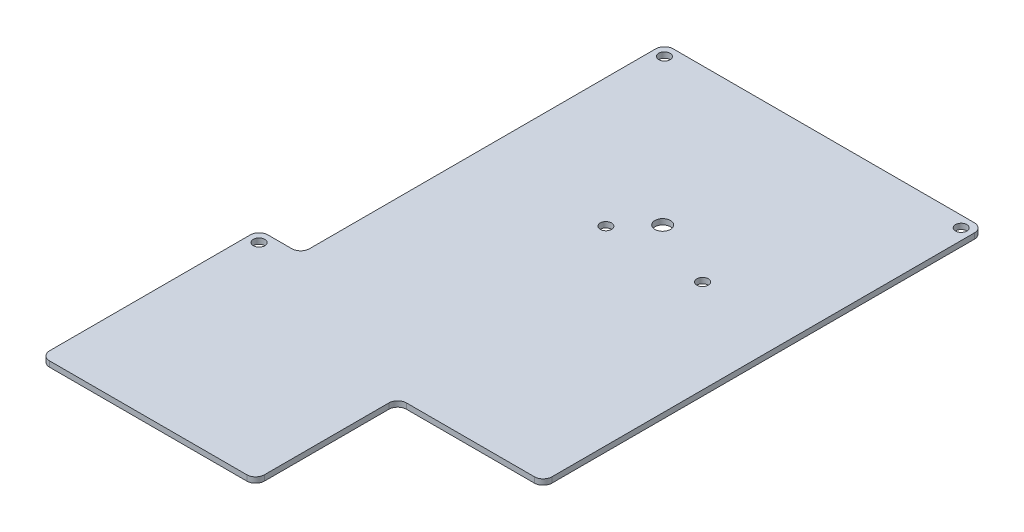
SolidWorks part; units mm, degrees
ref_plane "Front" through (0, 0, 0) normal (0, 0, 1) x (1, 0, 0)
ref_plane "Top" through (0, 0, 0) normal (0, 1, 0) x (1, 0, 0)
ref_plane "Right" through (0, 0, 0) normal (1, 0, 0) x (0, 0, -1)
sketch "Sketch1" plane through (0, 0, 0) normal (0, 1, 0) x (1, 0, 0)
  line L1 (-46, -63.5) -> (46, -63.5)
  line L2 (-46, -63.5) -> (-46, 63.5)
  line L3 (-46, 63.5) -> (46, 63.5)
  line L4 (46, -63.5) -> (46, 63.5)
  line L5 (-46, -63.5) -> (46, 63.5) construction
  line L6 (-46, 63.5) -> (46, -63.5) construction
  point P0 (0, 0)
  dimension "D1" = 127
  dimension "D2" = 92
extrude "Boss-Extrude1" add sketch "Sketch1" along normal blind 1.6
hole_wizard "#4 Clearance Hole1" positions "Sketch4" profile "Sketch5" hole size "#4" standard "ANSI Inch"
sketch "Sketch4" plane through (0, 1.6, 0) normal (0, 1, 0) x (1, 0, 0)
  line L2 (46, 63.5) -> (-46, 63.5) construction
  line L3 (-46, 63.5) -> (-46, -63.5) construction
  line L4 (-8.85, 9.46) -> (19.05, 9.46)
  point P22 (19.05, 9.46)
  point P24 (-8.85, 9.46)
  dimension "D1" = 27.9
  dimension "D3" = 54.04
  dimension "D4" = 37.15
sketch "Sketch5" plane through (19.05, 1.6, -9.46) normal (1, 0, 0) x (0, 0, 1)
  line L0 (0, 0) -> (0, 19.7306)
  line L1 (0, 19.7306) -> (1.6319, 18.75)
  line L2 (1.6319, 18.75) -> (1.6319, 0)
  line L5 (1.6319, 0) -> (0, 0)
  line L10 (0, 19.7306) -> (-1.632, 18.75) construction
  line L11 (0, -6.35) -> (0, 107.95) construction
  dimension "Hole Dia." = 3.2639
  dimension "Hole Depth" = 18.75
  dimension "Drill Angle" = 118
hole_wizard "#8 Clearance Hole1" positions "Sketch6" profile "Sketch7" hole size "#8" standard "ANSI Inch"
sketch "Sketch6" plane through (0, 0, 0) normal (0, -1, 0) x (-1, 0, 0)
  circle A1 centre (0.9676, 17.9647) radius 1.524 construction
  point P0 (0.9676, 17.9647)
sketch "Sketch7" plane through (-0.9676, 0, -17.9647) normal (1, 0, 0) x (0, 0, -1)
  line L0 (0, 0) -> (0, 20.1007)
  line L1 (0, 20.1007) -> (2.2479, 18.75)
  line L2 (2.2479, 18.75) -> (2.2479, 0)
  line L5 (2.2479, 0) -> (0, 0)
  line L10 (0, 20.1007) -> (-2.2479, 18.75) construction
  line L11 (0, -6.35) -> (0, 107.95) construction
  dimension "Hole Dia." = 4.4958
  dimension "Hole Depth" = 18.75
  dimension "Drill Angle" = 118
sketch "Sketch8" plane through (0, 0, 0) normal (0, 1, 0) x (1, 0, 0)
  line L0 (-46, -63.5) -> (46, -63.5) construction
  line L1 (4, -41.5) -> (-58, -41.5)
  line L2 (4, -41.5) -> (4, -104.5)
  line L3 (4, -104.5) -> (-58, -104.5)
  line L4 (-58, -41.5) -> (-58, -104.5)
  line L5 (4, -41.5) -> (-58, -104.5) construction
  line L6 (4, -104.5) -> (-58, -41.5) construction
  line L7 (-46, 63.5) -> (-46, -63.5) construction
  point P0 (-27, -73)
  dimension "D1" = 22
  dimension "D2" = 50
  dimension "D3" = 62
  dimension "D4" = 63
extrude "Boss-Extrude2" add sketch "Sketch8" along normal blind 1.6
hole_wizard "#4 Clearance Hole2" positions "Sketch2" profile "Sketch3" hole size "#4" standard "ANSI Inch"
sketch "Sketch2" plane through (0, 1.6, 0) normal (0, 1, 0) x (1, 0, 0)
  line L1 (-42.825, 60.325) -> (42.825, 60.325)
  line L2 (-42.825, 60.325) -> (-42.825, -60.325)
  line L3 (-42.825, -60.325) -> (42.825, -60.325)
  line L4 (42.825, 60.325) -> (42.825, -60.325)
  line L5 (-42.825, 60.325) -> (42.825, -60.325) construction
  line L6 (-42.825, -60.325) -> (42.825, 60.325) construction
  line L9 (46, -63.5) -> (46, 63.5) construction
  line L10 (4, -63.5) -> (46, -63.5) construction
  line L11 (-46, -41.5) -> (-58, -41.5) construction
  line L12 (-58, -41.5) -> (-58, -104.5) construction
  point P0 (-42.825, 60.325)
  point P2 (42.825, 60.325)
  point P118 (-54.82, -44.68)
  dimension "D1" = 3.175
  dimension "D2" = 3.175
  dimension "D3" = 3.18
  dimension "D4" = 3.18
sketch "Sketch3" plane through (-42.825, 1.6, -60.325) normal (1, 0, 0) x (0, 0, 1)
  line L0 (0, 0) -> (0, 50.9806)
  line L1 (0, 50.9806) -> (1.6319, 50)
  line L2 (1.6319, 50) -> (1.6319, 0)
  line L5 (1.6319, 0) -> (0, 0)
  line L10 (0, 50.9806) -> (-1.632, 50) construction
  line L11 (0, -6.35) -> (0, 107.95) construction
  dimension "Hole Dia." = 3.2639
  dimension "Hole Depth" = 50
  dimension "Drill Angle" = 118
fillet "Fillet1" radius 2.54 8 edges at (46, 0.8, 63.5) (46, 0.8, -63.5) (-46, 0.8, -63.5) (4, 0.8, 63.5) (4, 0.8, 104.5) (-58, 0.8, 104.5) (-58, 0.8, 41.5) (-46, 0.8, 41.5)
ref_point "PCB_ORIGIN"
sketch "TOP_KEEPOUT" plane through (0, 1.6, 0) normal (0, 1, 0) x (1, 0, 0)
  circle A0 centre (-8.85, 9.46) radius 3.429
  circle A1 centre (19.05, 9.46) radius 3.429
  circle A2 centre (42.825, 60.325) radius 3.429
  circle A3 centre (-42.825, 60.325) radius 3.429
  circle A6 centre (-54.82, -44.68) radius 3.429
  dimension "D1" = 6.858
sketch "BOTTOM_KEEPOUT" plane through (0, 0, 0) normal (0, -1, 0) x (1, 0, 0)
  line L1 (26.67, -45.02) -> (-26.7462, -45.02)
  line L2 (26.67, -45.02) -> (26.67, 56.58)
  line L3 (26.67, 56.58) -> (-26.7462, 56.58)
  line L4 (-26.7462, -45.02) -> (-26.7462, 56.58)
  line L5 (26.67, -41.464) -> (26.67, 55.056) construction
  line L6 (25.146, 56.58) -> (-25.2222, 56.58) construction
  line L8 (-26.7462, 55.056) -> (-26.7462, -40.7166) construction
  line L13 (-11.5062, -45.02) -> (23.114, -45.02) construction
  circle A2 centre (42.825, -60.325) radius 3.937
  circle A3 centre (-42.825, -60.325) radius 3.937
  circle A4 centre (-54.82, 44.68) radius 3.937
  dimension "D1" = 7.874
sketch "TOP_CONN_POS" plane through (0, 1.6, 0) normal (0, 1, 0) x (1, 0, 0)
  line L0 (6.35, -35.308) -> (6.35, -45.308)
  line L1 (-37.936, 28.7076) -> (-37.936, 18.7076)
  line L2 (1.35, -40.308) -> (11.35, -40.308)
  line L3 (-42.936, 23.7076) -> (-32.936, 23.7076)
  line L4 (0, 60.436) -> (0, 50.436)
  line L5 (-5, 55.436) -> (5, 55.436)
  line L6 (-37.936, -5.35) -> (-37.936, 52.7652) construction
  line L7 (-43.524, 23.7076) -> (-32.348, 23.7076) construction
  line L8 (0, 61.024) -> (0, 49.848) construction
  line L9 (-29.0576, 55.436) -> (29.0576, 55.436) construction
  line L10 (37.936, 28.7076) -> (37.936, 18.7076)
  line L11 (32.936, 23.7076) -> (42.936, 23.7076)
  line L12 (43.524, 23.7076) -> (32.348, 23.7076) construction
  line L13 (37.936, 52.7652) -> (37.936, -5.35) construction
  line L14 (37.936, -25.0576) -> (37.936, -35.0576)
  line L15 (32.936, -30.0576) -> (42.936, -30.0576)
  line L16 (37.936, -52.7652) -> (37.936, -7.35) construction
  line L17 (43.524, -30.0576) -> (32.348, -30.0576) construction
  line L18 (0, -50.436) -> (0, -60.436)
  line L19 (-5, -55.436) -> (5, -55.436)
  line L20 (29.0576, -55.436) -> (-29.0576, -55.436) construction
  line L21 (0, -61.024) -> (0, -49.848) construction
  line L22 (6.35, -45.896) -> (6.35, -34.72) construction
  line L23 (-16.3576, -40.308) -> (29.0576, -40.308) construction
  line L24 (-41.4, -141.4918) -> (-41.4, -151.4918)
  line L25 (-46.4, -146.4918) -> (-36.4, -146.4918)
  line L26 (-41.4, -167.6418) -> (-41.4, -157.6418)
  line L27 (-46.4, -162.6418) -> (-36.4, -162.6418)
  line L28 (-0.6, -67.345) -> (-0.6, -77.345)
  line L29 (-5.6, -72.345) -> (4.4, -72.345)
  line L30 (4, -72.345) -> (-11.4, -72.345) construction
  line L31 (-0.6, -77.67) -> (-0.6, -67.02) construction
  line L32 (-41.4, -155.8168) -> (-41.4, -169.4668) construction
  line L33 (-46, -162.6418) -> (-30.92, -162.6418) construction
  line L34 (-46, -146.4918) -> (-30.92, -146.4918) construction
  line L35 (-41.4, -139.6668) -> (-41.4, -153.3168) construction
  point P2 (6.35, -40.308)
  point P9 (-37.936, 23.7076)
  point P14 (0, 55.436)
  point P17 (-41.4, -146.4918)
  point P29 (37.936, 23.7076)
  point P40 (37.936, -30.0576)
  point P50 (0, -55.436)
  point P53 (-41.4, -162.6418)
  point P66 (-0.6, -72.345)
  dimension "D1" = 10
  dimension "D2" = 0
  dimension "D3" = 0
  dimension "D4" = 0
  dimension "D5" = 0
  dimension "D6" = 0
  dimension "D7" = 0
  dimension "D8" = 0
  dimension "D9" = 0
  dimension "D10" = 0
  dimension "D11" = 0
  dimension "D12" = 0
  dimension "D13" = 0
  dimension "D14" = 0
  dimension "D15" = 0
  dimension "D16" = 0
  dimension "D17" = 0
  dimension "D18" = 0
  dimension "D19" = 0
sketch "BOTTOM_CONN_POS" plane through (0, 1.6, 0) normal (0, 1, 0) x (1, 0, 0)
  line L2 (-41.7687, 26.7669) -> (-41.7687, 16.7669)
  line L3 (-46.7687, 21.7669) -> (-36.7687, 21.7669)
  line L4 (-17.2529, 63.5) -> (-17.2529, 48.1) construction
  line L5 (-25.5779, 58.9) -> (-8.9279, 58.9) construction
  line L6 (-41.7687, 45.4169) -> (-41.7687, 35.4169)
  line L7 (-46.7687, 40.4169) -> (-36.7687, 40.4169)
  line L8 (-41.7687, -41.17) -> (-41.7687, -51.17)
  line L9 (-46.7687, -46.17) -> (-36.7687, -46.17)
  line L10 (-41.7687, -53.82) -> (-41.7687, -63.82)
  line L11 (-46.7687, -58.82) -> (-36.7687, -58.82)
  line L12 (-41.7687, -66.47) -> (-41.7687, -76.47)
  line L13 (-46.7687, -71.47) -> (-36.7687, -71.47)
  line L14 (0.6971, 63.5) -> (0.6971, 48.1) construction
  line L15 (-46, -131.2896) -> (-30.6, -131.2896) construction
  line L16 (-46, -135.3418) -> (-30.6, -135.3418) construction
  line L17 (-46, -35.1047) -> (-30.6, -35.1047) construction
  line L18 (-39, -24.955) -> (-39, -34.955)
  line L19 (-44, -29.955) -> (-34, -29.955)
  line L32 (-39, -34.655) -> (-39, -25.255) construction
  line L33 (-42.65, -29.955) -> (-35.5, -29.955) construction
  line L40 (39.35, -41.555) -> (39.35, -51.555)
  line L41 (34.35, -46.555) -> (44.35, -46.555)
  line L42 (-41.4, 20.4523) -> (-41.4, 10.4523)
  line L43 (-46.4, 15.4523) -> (-36.4, 15.4523)
  line L44 (39.35, -24.455) -> (39.35, -34.455)
  line L45 (34.35, -29.455) -> (44.35, -29.455)
  line L46 (39.35, -39.355) -> (39.35, -53.755) construction
  line L47 (35.85, -46.555) -> (43, -46.555) construction
  line L48 (35.85, -29.455) -> (43, -29.455) construction
  line L49 (-41.4, 20.7773) -> (-41.4, 10.1273) construction
  line L50 (-46, 15.4523) -> (-30.6, 15.4523) construction
  line L51 (-41.4, 33.1023) -> (-41.4, 23.1023)
  line L52 (-46.4, 28.1023) -> (-36.4, 28.1023)
  line L53 (-41.4, 1.0205) -> (-41.4, -8.9795)
  line L54 (-46.4, -3.9795) -> (-36.4, -3.9795)
  line L61 (-46, 28.1023) -> (-30.6, 28.1023) construction
  line L62 (46, -3.9795) -> (30.92, -3.9795) construction
  line L63 (-41.4, 20.6205) -> (-41.4, 10.6205)
  line L64 (-46.4, 15.6205) -> (-36.4, 15.6205)
  line L65 (46, 15.6205) -> (30.92, 15.6205) construction
  line L66 (-41.4, 40.2205) -> (-41.4, 30.2205)
  line L67 (-46.4, 35.2205) -> (-36.4, 35.2205)
  line L68 (46, 35.2205) -> (30.92, 35.2205) construction
  line L69 (-27.975, 63.9) -> (-27.975, 53.9)
  line L70 (-32.975, 58.9) -> (-22.975, 58.9)
  line L71 (24.3598, 58.9) -> (10.7098, 58.9) construction
  line L72 (17.5348, 63.5) -> (17.5348, 48.42) construction
  line L73 (-10.825, 63.9) -> (-10.825, 53.9)
  line L74 (-15.825, 58.9) -> (-5.825, 58.9)
  line L75 (46, 35.275) -> (30.6, 35.275) construction
  line L76 (7.825, 63.9) -> (7.825, 53.9)
  line L77 (2.825, 58.9) -> (12.825, 58.9)
  line L78 (46, 15.675) -> (30.6, 15.675) construction
  line L79 (26.475, 63.9) -> (26.475, 53.9)
  line L80 (21.475, 58.9) -> (31.475, 58.9)
  line L81 (46, -3.925) -> (30.6, -3.925) construction
  point P13 (-41.7687, 21.7669)
  point P24 (-41.7687, 40.4169)
  point P29 (-41.7687, -46.17)
  point P34 (-41.7687, -58.82)
  point P39 (-41.7687, -71.47)
  point P56 (-39, -29.955)
  point P105 (39.35, -46.555)
  point P110 (-41.4, 15.4523)
  point P115 (39.35, -29.455)
  point P135 (-41.4, 28.1023)
  point P140 (-41.4, -3.9795)
  point P151 (-41.4, 15.6205)
  point P161 (-41.4, 35.2205)
  point P169 (-27.975, 58.9)
  point P179 (-10.825, 58.9)
  point P188 (7.825, 58.9)
  point P197 (26.475, 58.9)
  dimension "D2" = 10
  dimension "D3" = 0
  dimension "D4" = 0
  dimension "D5" = 10
  dimension "D6" = 10
  dimension "D7" = 10
  dimension "D8" = 10
  dimension "D9" = 0
  dimension "D10" = 85.1196
  dimension "D11" = 76.5218
  dimension "D12" = 36.3653
  dimension "D13" = 10
  dimension "D16" = 0
  dimension "D17" = 0
  dimension "D24" = 0
  dimension "D25" = 0
  dimension "D26" = 0
  dimension "D27" = 0
  dimension "D28" = 0
  dimension "D29" = 10
  dimension "D30" = 10
  dimension "D31" = 0
  dimension "D32" = 0
  dimension "D33" = 10
  dimension "D34" = 0
  dimension "D35" = 10
  dimension "D36" = 0
  dimension "D37" = 10
  dimension "D38" = 0
  dimension "D39" = 0
  dimension "D40" = 10
  dimension "D41" = 0
  dimension "D42" = 10
  dimension "D43" = 0
  dimension "D44" = 10
  dimension "D45" = 0
sketch "ARDUINO_MEGA_POSITIONS" plane through (0, 1.6, 0) normal (0, 1, 0) x (1, 0, 0)
  line L4 (22.86, -9.59) -> (22.86, -24.83) construction
  line L48 (22.86, -24.83) -> (25.4, -24.83) construction
  line L49 (25.4, -24.83) -> (25.4, -9.59) construction
  line L50 (23.622, -23.052) -> (23.622, -24.068) construction
  line L52 (23.622, -24.068) -> (24.638, -24.068) construction
  line L54 (24.638, -24.068) -> (24.638, -23.052) construction
  line L56 (22.86, -9.59) -> (22.86, -24.83)
  line L58 (22.86, -24.83) -> (25.4, -24.83)
  line L60 (25.4, -24.83) -> (25.4, -9.59)
  line L62 (23.622, -23.052) -> (23.622, -24.068)
  line L63 (23.622, -24.068) -> (24.638, -24.068)
  line L64 (24.638, -24.068) -> (24.638, -23.052)
  line L65 (-25.4762, -13.654) -> (-25.4762, -33.974) construction
  line L66 (-22.9362, -33.974) -> (-22.9362, -13.654) construction
  line L67 (-25.4762, -33.974) -> (-22.9362, -33.974) construction
  line L68 (-25.4762, -13.654) -> (-25.4762, -33.974)
  line L69 (-23.6982, -32.196) -> (-24.7142, -32.196)
  line L70 (-24.7142, -32.196) -> (-24.7142, -33.212)
  line L71 (-24.7142, -33.212) -> (-23.6982, -33.212)
  line L72 (-23.6982, -33.212) -> (-23.6982, -32.196)
  line L73 (-23.6982, -32.196) -> (-24.7142, -32.196)
  line L74 (-24.7142, -32.196) -> (-24.7142, -33.212)
  line L75 (-24.7142, -33.212) -> (-23.6982, -33.212)
  line L76 (-23.6982, -33.212) -> (-23.6982, -32.196)
  line L77 (-22.9362, -33.974) -> (-22.9362, -13.654)
  line L78 (-25.4762, -33.974) -> (-22.9362, -33.974)
  dimension "D1" = 0
